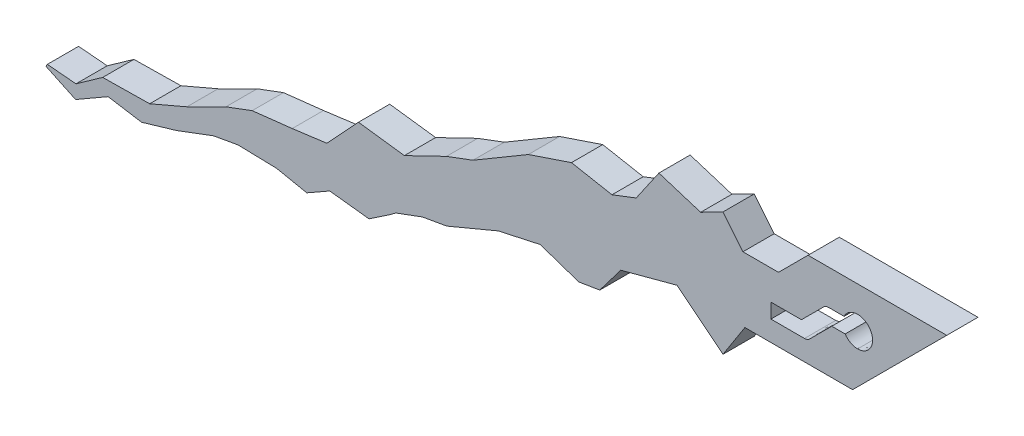
SolidWorks part; units mm, degrees
ref_plane "Ebene vorne" through (0, 0, 0) normal (0, 0, 1) x (1, 0, 0)
ref_plane "Ebene oben" through (0, 0, 0) normal (0, 1, 0) x (1, 0, 0)
ref_plane "Ebene rechts" through (0, 0, 0) normal (1, 0, 0) x (0, 0, -1)
sketch "Model" plane through (0, 0, 0) normal (0, 0, 1) x (1, 0, 0)
  line L48 (76.8642, 17.5634) -> (75.5799, 17.5634)
  line L49 (75.5799, 17.5634) -> (73.461, 15.4445)
  line L50 (73.3024, 22.3262) -> (70.4669, 19.4902)
  line L51 (72.9622, 15.2378) -> (69.7387, 15.2378)
  line L52 (69.7387, 15.2378) -> (69.7387, 16.6489)
  line L53 (69.7387, 16.6489) -> (72.67, 16.6489)
  line L54 (72.67, 16.6489) -> (74.7889, 18.7678)
  line L55 (70.4669, 19.4902) -> (67.0522, 19.4902)
  line L56 (75.2877, 18.9745) -> (76.7633, 18.9745)
  line L58 (67.0522, 19.4902) -> (65.1377, 21.8454)
  line L59 (65.1377, 21.8454) -> (62.991, 20.7426)
  line L60 (62.991, 20.7426) -> (58.9841, 22.0027)
  line L61 (58.9841, 22.0027) -> (56.803, 18.8388)
  line L62 (56.803, 18.8388) -> (54.4795, 17.9444)
  line L63 (54.4795, 17.9444) -> (50.59, 18.6713)
  line L64 (50.59, 18.6713) -> (46.4536, 17.279)
  line L65 (46.4536, 17.279) -> (41.1341, 14.1429)
  line L66 (41.1341, 14.1429) -> (38.5897, 13.1928)
  line L67 (38.5897, 13.1928) -> (34.5476, 11.2338)
  line L68 (34.5476, 11.2338) -> (30.1385, 11.806)
  line L69 (30.1385, 11.806) -> (27.108, 8.5409)
  line L70 (27.108, 8.5409) -> (23.78, 8.1001)
  line L71 (23.78, 8.1001) -> (19.9361, 7.6648)
  line L72 (19.9361, 7.6648) -> (17.4121, 6.7217)
  line L73 (17.4121, 6.7217) -> (13.6665, 4.8514)
  line L74 (13.6665, 4.8514) -> (10.0942, 3.3184)
  line L75 (10.0942, 3.3184) -> (5.5816, 3.2524)
  line L76 (5.5816, 3.2524) -> (3.0187, 1.4378)
  line L77 (3.0187, 1.4378) -> (0.2676, 1.6817)
  line L78 (0.2676, 1.6817) -> (0.1393, 1.45)
  line L79 (0.1393, 1.45) -> (2.9813, 0.1127)
  line L80 (2.9813, 0.1127) -> (6.1038, 1.9118)
  line L81 (6.1038, 1.9118) -> (9.3163, 1.3905)
  line L82 (9.3163, 1.3905) -> (12.655, 2.3753)
  line L83 (12.655, 2.3753) -> (16.2205, 3.7167)
  line L84 (16.2205, 3.7167) -> (18.5922, 4.1362)
  line L85 (18.5922, 4.1362) -> (22.2788, 4.0404)
  line L86 (22.2788, 4.0404) -> (25.1785, 3.4514)
  line L87 (25.1785, 3.4514) -> (27.3781, 4.7079)
  line L88 (27.3781, 4.7079) -> (31.1542, 4.2752)
  line L89 (31.1542, 4.2752) -> (33.1201, 5.6028)
  line L90 (33.1201, 5.6028) -> (33.7439, 6.0592)
  line L91 (33.7439, 6.0592) -> (36.2735, 6.9932)
  line L92 (36.2735, 6.9932) -> (38.6239, 7.4095)
  line L93 (38.6239, 7.4095) -> (43.5681, 9.4807)
  line L94 (43.5681, 9.4807) -> (47.5879, 10.3601)
  line L95 (47.5879, 10.3601) -> (51.2897, 9.1002)
  line L96 (51.2897, 9.1002) -> (53.3064, 9.4304)
  line L97 (53.3064, 9.4304) -> (55.321, 12.0932)
  line L98 (55.321, 12.0932) -> (60.73, 13.5423)
  line L99 (60.73, 13.5423) -> (65.1399, 10.0082)
  line L100 (65.1399, 10.0082) -> (67.2413, 13.2867)
  line L101 (67.2413, 13.2867) -> (77.5807, 13.2867)
  line L102 (77.5807, 13.2867) -> (86.6202, 22.3262)
  line L103 (86.6202, 22.3262) -> (73.3024, 22.3262)
  spline S0 degree 3 poles (78.062, 19.7974) (78.8565, 19.7974) (79.5006, 19.1533) (79.5007, 18.3588) knots 0 0 0 0 1 1 1 1
  spline S1 degree 3 poles (79.5007, 18.3588) (79.5006, 17.5642) (78.8565, 16.9202) (78.062, 16.9201) knots 0 0 0 0 1 1 1 1
  spline S2 degree 3 poles (78.062, 16.9201) (77.5802, 16.9204) (77.1306, 17.1619) (76.8642, 17.5634) knots 0 0 0 0 1 1 1 1
  spline S3 degree 3 poles (73.461, 15.4445) (73.3287, 15.3122) (73.1493, 15.2378) (72.9622, 15.2378) knots 0 0 0 0 1 1 1 1
  spline S4 degree 3 poles (74.7889, 18.7678) (74.9212, 18.9001) (75.1006, 18.9744) (75.2877, 18.9745) knots 0 0 0 0 1 1 1 1
  spline S5 degree 3 poles (76.7633, 18.9745) (77.0011, 19.4765) (77.5066, 19.7968) (78.062, 19.7974) knots 0 0 0 0 1 1 1 1
extrude "Aufsatz-Linear austragen1" add sketch "Model" along normal blind 3
